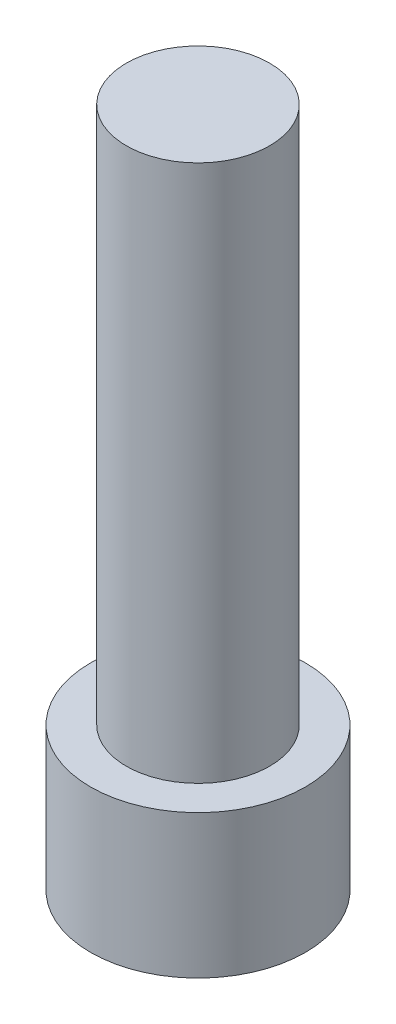
SolidWorks part; units mm, degrees
ref_plane "Front Plane" through (0, 0, 0) normal (0, 0, 1) x (1, 0, 0)
ref_plane "Top Plane" through (0, 0, 0) normal (0, 1, 0) x (1, 0, 0)
ref_plane "Right Plane" through (0, 0, 0) normal (1, 0, 0) x (0, 0, -1)
sketch "Sketch1" plane through (0, 0, 0) normal (0, 1, 0) x (1, 0, 0)
  circle A0 centre (0, 0) radius 9
extrude "Boss-Extrude1" add sketch "Sketch1" along normal blind 12
sketch "Sketch2" plane through (0, 12, 0) normal (0, 1, 0) x (1, 0, 0)
  circle A0 centre (0, 0) radius 6
extrude "Boss-Extrude2" add sketch "Sketch2" along normal blind 45
